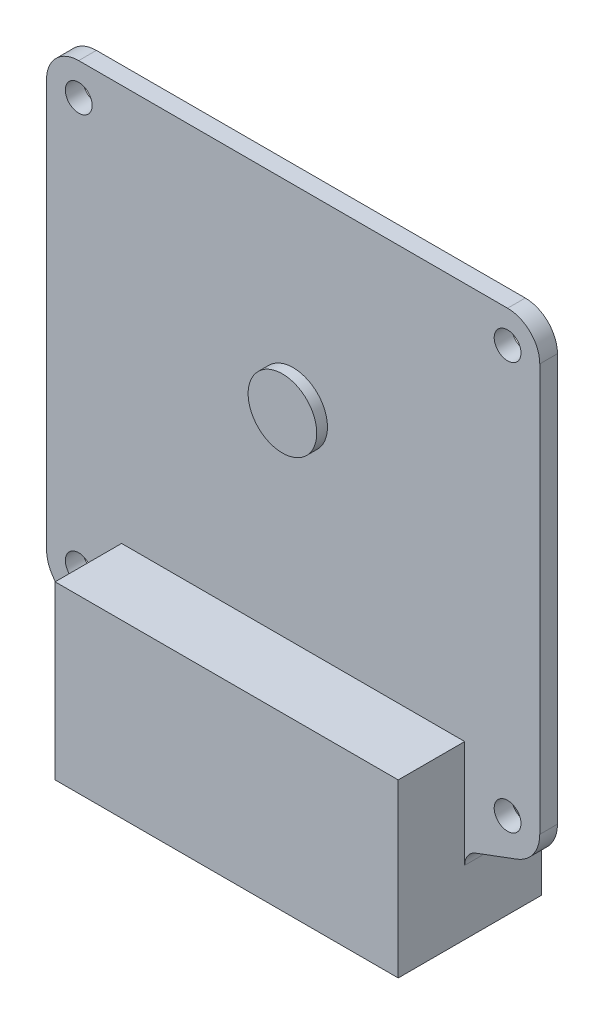
SolidWorks part; units mm, degrees
ref_plane "Front Plane" through (0, 0, 0) normal (0, 0, 1) x (1, 0, 0)
ref_plane "Top Plane" through (0, 0, 0) normal (0, 1, 0) x (1, 0, 0)
ref_plane "Right Plane" through (0, 0, 0) normal (1, 0, 0) x (0, 0, -1)
sketch "Sketch1" plane through (0, 0, 0) normal (0, 0, 1) x (1, 0, 0)
  line L0 (-20, 15) -> (20, 15) construction
  line L1 (-20, -23) -> (20, -23) construction
  line L2 (-20, 18) -> (20, 18)
  line L3 (-16, -35) -> (16, -35)
  line L4 (-23, 15) -> (-23, -23)
  line L5 (23, 15) -> (23, -23)
  line L6 (-27.3518, -23) -> (-27.3518, -29) construction
  line L7 (-27.3518, -29) -> (-27.3518, -35) construction
  line L8 (-27.3518, -29) -> (32.2638, -29) construction
  line L9 (-27.3518, -35) -> (32.2638, -35) construction
  line L10 (-16, -35) -> (-16, -29)
  line L11 (16, -35) -> (16, -29)
  line L12 (-20.8734, -26.0636) -> (-17.0471, -27.4916)
  line L13 (0, 21.7483) -> (0, -55.2269) construction
  line L15 (20.8734, -26.0636) -> (17.0471, -27.4916)
  circle A0 centre (0, 0) radius 3.2
  circle A1 centre (20, 15) radius 1.25
  circle A2 centre (-20, 15) radius 1.25
  circle A3 centre (-20, -23) radius 1.25
  circle A4 centre (20, -23) radius 1.25
  arc A5 (-20, 18) -> (-23, 15) centre (-20, 15) ccw
  arc A6 (23, 15) -> (20, 18) centre (20, 15) ccw
  arc A8 (-16, -29) -> (-17.0471, -27.4916) centre (-17.61, -29) ccw
  arc A9 (16, -29) -> (17.0471, -27.4916) centre (17.61, -29) cw
  arc A11 (-23, -23) -> (-20.8734, -26.0636) centre (-19.73, -23) ccw
  arc A12 (23, -23) -> (20.8734, -26.0636) centre (19.73, -23) cw
  point P5 (0, 15)
  point P10 (0, -23)
  point P18 (0, -35)
  dimension "D1" = 15
  dimension "D3" = 2.5
  dimension "D4" = 2.5
  dimension "D7" = 2.5
  dimension "D8" = 2.5
  dimension "D11" = 6
  dimension "D9" = 6
  dimension "D12" = 6.4
  dimension "D15" = 3.27
  dimension "D16" = 1.61
  dimension "D2" = 40
  dimension "D5" = 40
  dimension "D6" = 23
  dimension "D10" = 32
  dimension "D13" = 6
  dimension "D14" = 6
  dimension "D17" = 7.3518
extrude "Boss-Extrude1" add sketch "Sketch1" along normal blind 1.65
sketch "Sketch2" plane through (0, 0, 1.65) normal (0, 0, 1) x (1, 0, 0)
  line L0 (-16, -35) -> (16, -35) construction
  line L1 (-16, -19) -> (16, -19)
  line L2 (-16, -19) -> (-16, -35)
  line L3 (-16, -35) -> (16, -35)
  line L4 (16, -19) -> (16, -35)
  line L5 (-16, -19) -> (16, -35) construction
  line L6 (-16, -35) -> (16, -19) construction
  point P0 (0, -27)
  dimension "D1" = 16
  dimension "D2" = 32
extrude "Boss-Extrude2" add sketch "Sketch2" along normal blind 6.2
extrude "Boss-Extrude3" add sketch "Sketch1<2>" along normal offset from surface (2.65 mm away) 1 contours A0 region at (0, 0, 0) up to face at (0, -13.0147, 1.65) offset beyond the face yes
sketch "Sketch1<2>" plane through (0, 0, 0) normal (0, 0, 1) x (1, 0, 0) same geometry as "Sketch1"
sketch "Sketch3" plane through (0, 0, 0) normal (0, 0, -1) x (-1, 0, 0)
  line L1 (-16, -35) -> (16.03, -35)
  line L2 (-16, -35) -> (-16, -25)
  line L3 (-16, -25) -> (16.03, -25)
  line L4 (16.03, -35) -> (16.03, -25)
  dimension "D1" = 10
  dimension "D2" = 32.03
extrude "Boss-Extrude4" add sketch "Sketch3" along normal blind 5.5
